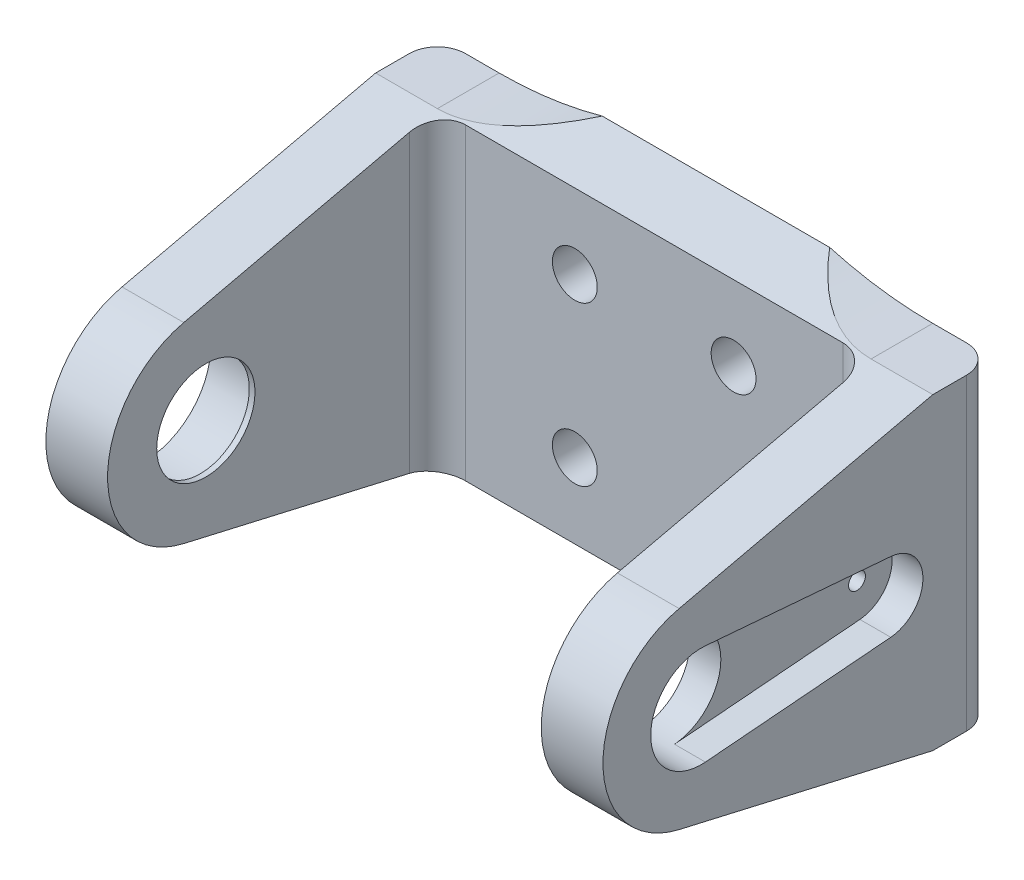
SolidWorks part; units mm, degrees
material "ABS"
ref_plane "Ön Düzlem" through (0, 0, 0) normal (0, 0, 1) x (1, 0, 0)
ref_plane "Üst Düzlem" through (0, 0, 0) normal (0, 1, 0) x (1, 0, 0)
ref_plane "Sağ Düzlem" through (0, 0, 0) normal (1, 0, 0) x (0, 0, -1)
sketch "Çizim1" plane through (0, 0, 0) normal (0, 1, 0) x (1, 0, 0)
  line L0 (-19.85, 0) -> (19.85, 0) construction
  line L1 (-19.85, -7) -> (-19.85, 20.9)
  line L2 (-19.85, -7) -> (-15.45, -7)
  line L3 (-15.45, -7) -> (-15.45, 16.5)
  line L4 (0, 0) -> (0, 16.5) construction
  line L5 (19.85, -7) -> (15.45, -7)
  line L6 (19.85, -7) -> (19.85, 20.9)
  line L7 (15.45, -7) -> (15.45, 16.5)
  line L8 (-15.45, 16.5) -> (15.45, 16.5)
  line L9 (-19.85, 20.9) -> (19.85, 20.9)
  point P4 (0, 0)
  dimension "D1" = 4.4
  dimension "D2" = 7
  dimension "D3" = 4.4
  dimension "D4" = 15.45
  dimension "D5" = 16.5
extrude "Yükseklik-Ekstrüzyon1" add sketch "Çizim1" along normal mid plane 28
sketch "Çizim2" plane through (0, 0, 0) normal (1, 0, 0) x (0, 0, -1)
  line L0 (-1.572, -6.8212) -> (20.9, -12)
  line L1 (20.9, -12) -> (20.9, 12)
  line L2 (-1.572, 6.8212) -> (20.9, 12)
  line L3 (0, 0) -> (20.9, 0) construction
  line L5 (20.9, -12) -> (20.9, -14)
  line L6 (20.9, 12) -> (20.9, 14)
  line L9 (-7, -14) -> (20.9, -14)
  line L10 (-7, 14) -> (-7, -14)
  line L11 (20.9, 14) -> (-7, 14)
  line L12 (20.9, -14) -> (20.9, 14)
  line L13 (-7, -14) -> (20.9, -14)
  line L14 (-7, 14) -> (-7, -14)
  line L15 (20.9, 14) -> (-7, 14)
  circle A0 centre (0, 0) radius 4.6 construction
  circle A1 centre (0, 0) radius 7
  point P8 (-7, 0)
  dimension "D1" = 9.2
  dimension "D3" = 24
  dimension "D5" = 0
extrude "Kes-Ekstrüzyon1" cut sketch "Çizim2" against normal through all contours A1 L14 L13 L5 L0 | A1 L2 L6 L15 L14 region at (0, -10.8054, -3.6874) region at (0, 10.8054, -3.6874)
sketch "Çizim3" plane through (0, 0, 0) normal (1, 0, 0) x (0, 0, -1)
  line L1 (20.9, -12) -> (20.9, 12) construction
  line L2 (20.9, -12) -> (20.9, -14) construction
  line L3 (-7, -14) -> (20.9, -14) construction
  line L4 (-7, 14) -> (-7, -14) construction
  line L5 (20.9, 14) -> (-7, 14) construction
  line L6 (20.9, 12) -> (20.9, 14) construction
  line L8 (-1.572, 6.8212) -> (20.9, 12)
  line L9 (20.9, -12) -> (20.9, 12)
  line L10 (20.9, -12) -> (20.9, -14)
  line L11 (-7, -14) -> (20.9, -14)
  line L12 (-7, 14) -> (-7, -14)
  line L13 (20.9, 14) -> (-7, 14)
  line L14 (20.9, 12) -> (20.9, 14)
  line L15 (-1.572, -6.8212) -> (20.9, -12)
  circle A0 centre (0, 0) radius 3.6 construction
  circle A1 centre (0, 0) radius 7
  circle A2 centre (0, 0) radius 7 construction
  dimension "D1" = 7.2
extrude "Kes-Ekstrüzyon3" cut sketch "Çizim3" along normal through all contours A1 L8 L14 L13 L12 | A1 L12 L11 L10 L15 region at (0, 10.8054, -3.6874) region at (0, -10.8054, -3.6874)
sketch "Çizim4" plane through (0, 0, -16.5) normal (0, 0, 1) x (1, 0, 0)
  line L0 (0, 0) -> (0, 14) construction
  line L1 (0, 0) -> (-14, 0) construction
  line L2 (-15.45, 10.986) -> (-19.85, 10.986)
  line L3 (-19.85, 6.8212) -> (-19.85, 12) construction
  line L4 (-19.85, 10.986) -> (-19.85, 14)
  line L5 (-19.85, 14) -> (19.85, 14)
  line L6 (-15.45, 10.986) -> (-15.45, -10.986)
  line L8 (-15.45, 10.986) -> (-15.45, -10.986)
  line L10 (15.45, 10.986) -> (19.85, 10.986)
  line L11 (19.85, 10.986) -> (19.85, 14)
  line L12 (15.45, -10.986) -> (15.45, 10.986)
  line L13 (-15.45, -10.986) -> (-19.85, -10.986)
  line L14 (-19.85, -10.986) -> (-19.85, -14)
  line L15 (-19.85, -14) -> (19.85, -14)
  line L16 (19.85, -10.986) -> (19.85, -14)
  line L17 (15.45, -10.986) -> (19.85, -10.986)
  line L22 (15.45, -10.986) -> (15.45, 10.986)
  line L23 (15.45, 10.986) -> (-15.45, 10.986)
  line L37 (15.45, 10.986) -> (-15.45, 10.986)
  line L38 (-15.45, -10.986) -> (15.45, -10.986)
  line L39 (-15.45, -10.986) -> (15.45, -10.986)
  circle A0 centre (0, 0) radius 14
  arc A1 (-15.45, 10.986) -> (-5.262, 12.9735) centre (-15.45, 38.0919) ccw
  arc A2 (-15.45, -10.986) -> (-5.262, -12.9735) centre (-15.45, -38.0919) cw
  arc A3 (15.45, -10.986) -> (5.262, -12.9735) centre (15.45, -38.0919) ccw
  arc A4 (15.45, 10.986) -> (5.262, 12.9735) centre (15.45, 38.0919) cw
  point P21 (0, 14)
  dimension "D2" = 28
  dimension "D1" = 0
extrude "Kes-Ekstrüzyon4" cut sketch "Çizim4" against normal through all contours A1 A0 | A4 A0 | A3 A0 | A2 A0 region at (-12.9763, 12.703, -16.5) region at (-12.9763, -12.703, -16.5) region at (12.9763, 12.703, -16.5) region at (12.9763, -12.703, -16.5)
sketch "Çizim6" plane through (19.85, 0, 0) normal (1, 0, 0) x (0, 0, -1)
  line L0 (0, 0) -> (13.3, 0) construction
  line L1 (13.5068, 2.4914) -> (0.2977, 3.5877)
  line L2 (13.5068, -2.4914) -> (0.2977, -3.5877)
  circle A0 centre (0, 0) radius 3.6
  circle A1 centre (13.3, 0) radius 2.5
  point P9 (15.8, 0)
  point P10 (-3.6, 0)
  dimension "D1" = 7.2
  dimension "D2" = 5
  dimension "D3" = 19.4
extrude "Kes-Ekstrüzyon6" cut sketch "Çizim6" against normal up to next contours A0 region at (19.85, 0, 0)
sketch "Çizim5" plane through (0, 0, -20.9) normal (0, 0, -1) x (-1, 0, 0)
  line L0 (0, 0) -> (0, -14) construction
  line L1 (5.6569, 5.6569) -> (-5.6569, -5.6569) construction
  line L2 (-5.6569, 5.6569) -> (5.6569, -5.6569) construction
  circle A0 centre (0, 0) radius 4
  circle A1 centre (0, 0) radius 14 construction
  circle A2 centre (-5.6569, 5.6569) radius 1.6
  circle A3 centre (-5.6569, -5.6569) radius 1.6
  circle A4 centre (5.6569, -5.6569) radius 1.6
  circle A5 centre (5.6569, 5.6569) radius 1.6
  point P10 (0, 0)
  point P13 (0, 0)
  dimension "D1" = 8
  dimension "D5" = 3.2
  dimension "D2" = 45
  dimension "D3" = 16
  dimension "D4" = 16
extrude "Kes-Ekstrüzyon5" cut sketch "Çizim5" against normal through all contours A3 | A2 | A5 | A4 region at (5.6569, 5.6569, -20.9) region at (5.6569, -5.6569, -20.9) region at (-5.6569, -5.6569, -20.9) region at (-5.6569, 5.6569, -20.9)
extrude "Kes-Ekstrüzyon7" cut sketch "Çizim6<3>" against normal blind 2.2 contours A0 L0 A1 L1 | L0 A0 L2 A1 | A1 region at (19.85, 1.6474, -6.9796) region at (19.85, -1.6474, -6.9796) region at (19.85, 1.7874, -11.6548)
sketch "Çizim6<3>" plane through (19.85, 0, 0) normal (1, 0, 0) x (0, 0, -1) same geometry as "Çizim6"
sketch "Çizim7" plane through (17.65, 0, 0) normal (1, 0, 0) x (0, 0, -1)
  circle A0 centre (13.3, 0) radius 0.6
  dimension "D1" = 13.3
  dimension "D2" = 1.2
extrude "Kes-Ekstrüzyon8" cut sketch "Çizim7" against normal up to next
sketch "Çizim9" plane through (-19.85, 0, 0) normal (-1, 0, 0) x (0, 0, 1)
  circle A0 centre (0, 0) radius 4.75
  circle A1 centre (0, 0) radius 3.5
  dimension "D1" = 9.5
  dimension "D2" = 7
extrude "Kes-Ekstrüzyon10" cut sketch "Çizim9" against normal up to next contours A1 region at (-19.85, 0, 0)
extrude "Kes-Ekstrüzyon11" cut sketch "Çizim9<3>" against normal blind 4
sketch "Çizim9<3>" plane through (-19.85, 0, 0) normal (-1, 0, 0) x (0, 0, 1) same geometry as "Çizim9"
fillet "Radyus1" radius 2 4 edges at (-19.85, 0, -20.9) (-15.45, 0, -16.5) (15.45, 0, -16.5) (19.85, 0, -20.9)
extrude "Kes-Ekstrüzyon12" cut sketch "Çizim5<3>" against normal blind 3 contours A0 region at (0, 0, -20.9)
sketch "Çizim5<3>" plane through (0, 0, -20.9) normal (0, 0, -1) x (-1, 0, 0) same geometry as "Çizim5"
chamfer "Pah1" distance 1.5 angle 45 1 edges at (-4, 0, -17.9)
sketch "Çizim10" plane through (0, 0, -16.5) normal (0, 0, 1) x (1, 0, 0)
  circle A0 centre (-5.6569, 5.6569) radius 2.75
  circle A1 centre (5.6569, 5.6569) radius 2.75
  circle A2 centre (5.6569, -5.6569) radius 2.75
  circle A3 centre (-5.6569, -5.6569) radius 2.75
  dimension "D1" = 5.5
extrude "Yükseklik-Ekstrüzyon2" [suppressed] add sketch "Çizim10" along normal blind 3
